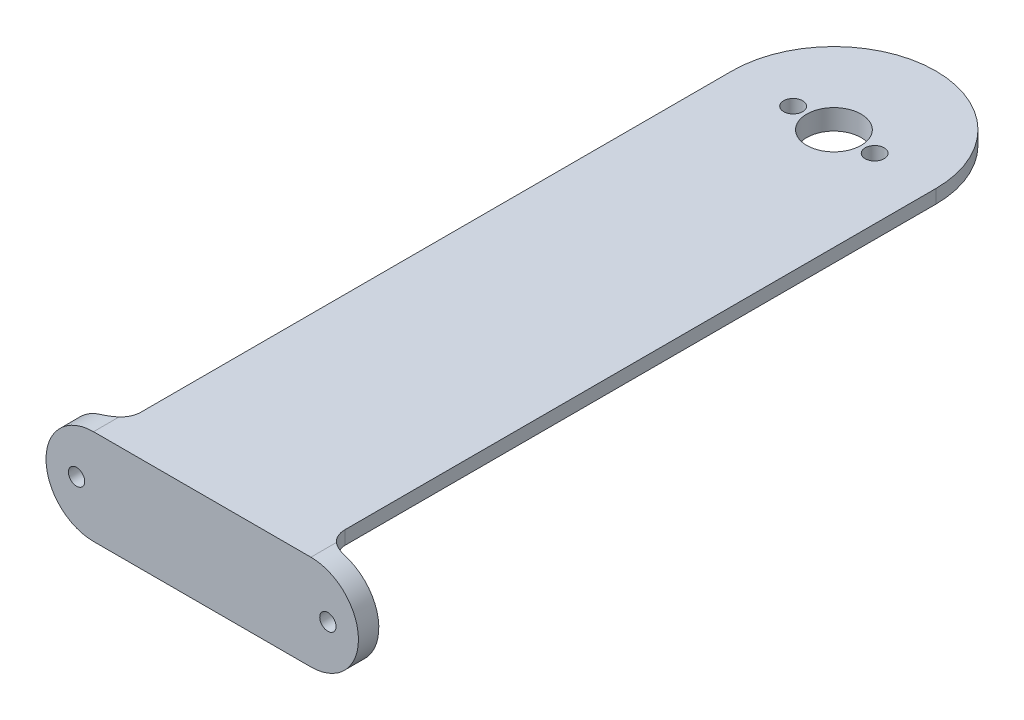
SolidWorks part; units mm, degrees
material "ABS"
ref_plane "Plan de face" through (0, 0, 0) normal (0, 0, 1) x (1, 0, 0)
ref_plane "Plan de dessus" through (0, 0, 0) normal (0, 1, 0) x (1, 0, 0)
ref_plane "Plan de droite" through (0, 0, 0) normal (1, 0, 0) x (0, 0, -1)
sketch "Esquisse1" plane through (0, 0, 0) normal (0, 1, 0) x (1, 0, 0)
  line L0 (-15, 0) -> (-15, -90)
  line L1 (-15, -90) -> (15, -90)
  line L2 (15, -90) -> (15, 0)
  circle A0 centre (0, 0) radius 4
  arc A1 (15, 0) -> (-15, 0) centre (0, 0) ccw
  dimension "D1" = 8
  dimension "D3" = 90
  dimension "D2" = 30
extrude "Boss.-Extru.1" add sketch "Esquisse1" along normal blind 2
sketch "Esquisse2" plane through (0, 0, 0) normal (0, -1, 0) x (1, 0, 0)
  circle A0 centre (0, 0) radius 7.75
  circle A1 centre (0, 0) radius 4 construction
  circle A2 centre (0, 0) radius 4
  dimension "D1" = 15.5
extrude "Boss.-Extru.2" add sketch "Esquisse2" along normal blind 1
sketch "Esquisse3" plane through (0, 0, 0) normal (0, -1, 0) x (1, 0, 0)
  circle A0 centre (0, 65) radius 3.75
  dimension "D1" = 7.5
  dimension "D2" = 65
extrude "Boss.-Extru.3" add sketch "Esquisse3" along normal blind 3
fillet "Congé1" radius 1 1 edges at (0, -3, 61.25)
sketch "Esquisse4" plane through (0, 2, 0) normal (0, 1, 0) x (1, 0, 0)
  line L0 (-6, 0) -> (6, 0) construction
  circle A0 centre (6, 0) radius 1.4
  circle A1 centre (-6, 0) radius 1.4
  dimension "D1" = 2.8
  dimension "D2" = 12
extrude "Enlèv. mat.-Extru.1" cut sketch "Esquisse4" against normal through all
sketch "Esquisse5" plane through (0, 0, 90) normal (0, 0, 1) x (1, 0, 0)
  line L0 (-16, -5) -> (16, -5) construction
  line L1 (-16, 2) -> (16, 2)
  line L2 (-16, -12) -> (16, -12)
  line L3 (-15, 2) -> (15, 2) construction
  line L4 (0, 2) -> (0, -12) construction
  arc A0 (-16, 2) -> (-16, -12) centre (-16, -5) ccw
  arc A1 (16, -12) -> (16, 2) centre (16, -5) ccw
  circle A2 centre (-18.5, -5) radius 1.2
  circle A3 centre (18.5, -5) radius 1.2
  point P2 (0, -5)
  point P11 (0, 2)
  dimension "D1" = 37
  dimension "D3" = 2.4
  dimension "D2" = 14
  dimension "D4" = 32
extrude "Boss.-Extru.4" add sketch "Esquisse5" along normal blind 3
fillet "Congé2" radius 3 3 edges at (0, 0, 90)
